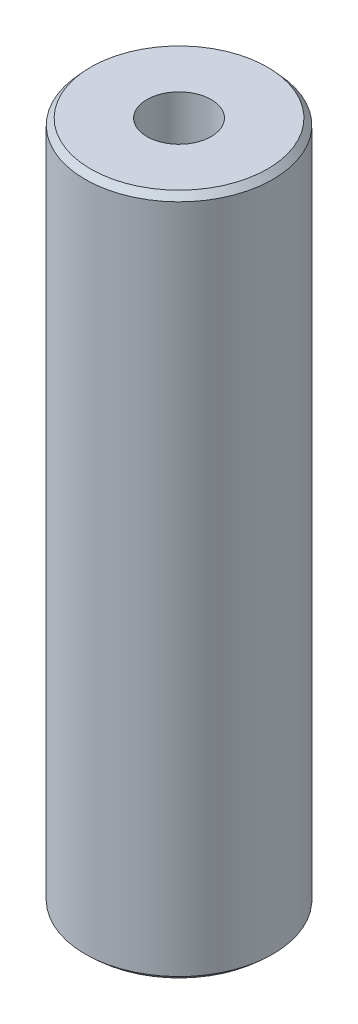
SolidWorks part; units mm, degrees
ref_plane "Front Plane" through (0, 0, 0) normal (0, 0, 1) x (1, 0, 0)
ref_plane "Top Plane" through (0, 0, 0) normal (0, 1, 0) x (1, 0, 0)
ref_plane "Right Plane" through (0, 0, 0) normal (1, 0, 0) x (0, 0, -1)
sketch "Sketch1" plane through (0, 0, 0) normal (0, 1, 0) x (1, 0, 0)
  circle A0 centre (0, 0) radius 45
  dimension "SHAFT_OD" = 90
extrude "Boss-Extrude1" add sketch "Sketch1" along normal blind 327.0914
sketch "Sketch2" plane through (0, 0, 0) normal (0, 1, 0) x (1, 0, 0)
  circle A0 centre (0, 0) radius 15.3991
  dimension "BORE_D" = 30.7982
extrude "Cut-Extrude1" cut sketch "Sketch2" along normal through all
chamfer "Chamfer1" distance 2.9477 angle 42.191 2 edges at (0, 327.0914, 45) (0, 0, 45) first distance on face at (0, 327.0914, 45) first distance on face at (0, 0, 15.3991)
